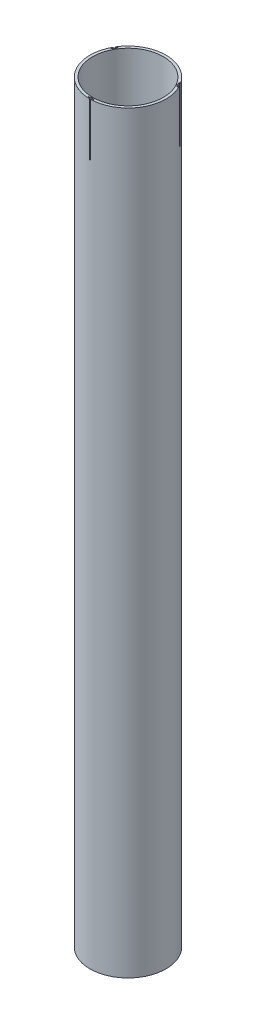
SolidWorks part; units mm, degrees
ref_plane "Front Plane" through (0, 0, 0) normal (0, 0, 1) x (1, 0, 0)
ref_plane "Top Plane" through (0, 0, 0) normal (0, 1, 0) x (1, 0, 0)
ref_plane "Right Plane" through (0, 0, 0) normal (1, 0, 0) x (0, 0, -1)
sketch "Sketch1" plane through (0, 0, 0) normal (0, 1, 0) x (1, 0, 0)
  circle A0 centre (0, 0) radius 57.5
  dimension "D1" = 115
extrude "Boss-Extrude1" add sketch "Sketch1" along normal mid plane 1140
ref_plane "Plane1" through (0, 490, 0) normal (0, 1, 0) x (1, 0, 0)
ref_plane "Plane2" through (0, 570, 0) normal (0, 1, 0) x (1, 0, 0)
shell "Shell1" thickness 4 removed face at (0, 570, 57.5) removed face at (0, -570, 57.5)
sketch "Sketch2" plane through (0, 570, 0) normal (0, 1, 0) x (1, 0, 0)
  line L0 (0, 64.7023) -> (0, -68.4384) construction
  line L1 (1, -57.4913) -> (1, -56.5087)
  line L13 (4, -56.5087) -> (4, -55.5087)
  line L14 (1, -56.5087) -> (4, -56.5087)
  line L15 (4, -55.5087) -> (0, -54.5087)
  line L16 (-4, -55.5087) -> (0, -54.5087)
  line L17 (-4, -56.5087) -> (-4, -55.5087)
  line L18 (-1, -56.5087) -> (-4, -56.5087)
  line L19 (-1, -57.4913) -> (-1, -56.5087)
  arc A0 (-1, -57.4913) -> (1, -57.4913) centre (0, 0) ccw
  circle A1 centre (0, 0) radius 57.5 construction
extrude "Cut-Extrude4" cut sketch "Sketch2" against normal blind 80
ref_axis "Axis1" through (0, -777.4745, 0) along (0, 1, 0)
pattern_circular "CirPattern1" count 3 over 360 about axis through (0, -777.4745, 0) along (0, 1, 0) of "Cut-Extrude4"
ref_plane "Plane3" through (0, -570, 0) normal (0, -1, 0) x (-1, 0, 0)
sketch "Sketch3" plane through (0, -570, 0) normal (0, -1, 0) x (-1, 0, 0)
  line L0 (4.4821, 53.3119) -> (0, 0) construction
  line L1 (4.4821, 53.3119) -> (2.1363, 25.4104)
  line L2 (-22.7744, 48.4105) -> (0, 0) construction
  line L3 (-22.7744, 48.4105) -> (-10.8534, 23.0706)
  circle A0 centre (0, 0) radius 53.5 construction
  circle A1 centre (0, 0) radius 25.5 construction
  arc A2 (4.4821, 53.3119) -> (-22.7744, 48.4105) centre (0, 0) ccw
  arc A3 (2.1363, 25.4104) -> (-10.8551, 23.0742) centre (0, 0) ccw
  point P9 (0, 0)
  point P10 (0, 0)
  point P11 (0, 0)
  point P12 (0, 0)
  point P13 (0, 0)
sketch "Sketch4" plane through (0, -570, 0) normal (0, -1, 0) x (-1, 0, 0)
  line L0 (0, 0) -> (4.4821, 53.3119) construction
  line L1 (4.4821, 53.3119) -> (2.1363, 25.4104)
  line L2 (-10.8551, 23.0742) -> (-22.7744, 48.4105)
  line L3 (-4.4821, -53.3119) -> (4.4821, 53.3119) construction
  line L4 (-4.4821, -53.3119) -> (-2.1363, -25.4104)
  line L5 (22.7744, -48.4105) -> (-22.7744, 48.4105) construction
  line L6 (10.8551, -23.0742) -> (22.7744, -48.4105)
  arc A0 (4.4821, 53.3119) -> (-22.7744, 48.4105) centre (0, 0) ccw
  arc A1 (2.1363, 25.4104) -> (-10.8551, 23.0742) centre (0, 0) ccw
  arc A2 (-2.1363, -25.4104) -> (10.8551, -23.0742) centre (0, 0) ccw
  arc A3 (-4.4821, -53.3119) -> (22.7744, -48.4105) centre (0, 0) ccw
  point P11 (0, 0)
  point P14 (0, 0)
extrude "Boss-Extrude3" add sketch "Sketch4" against normal blind 5
